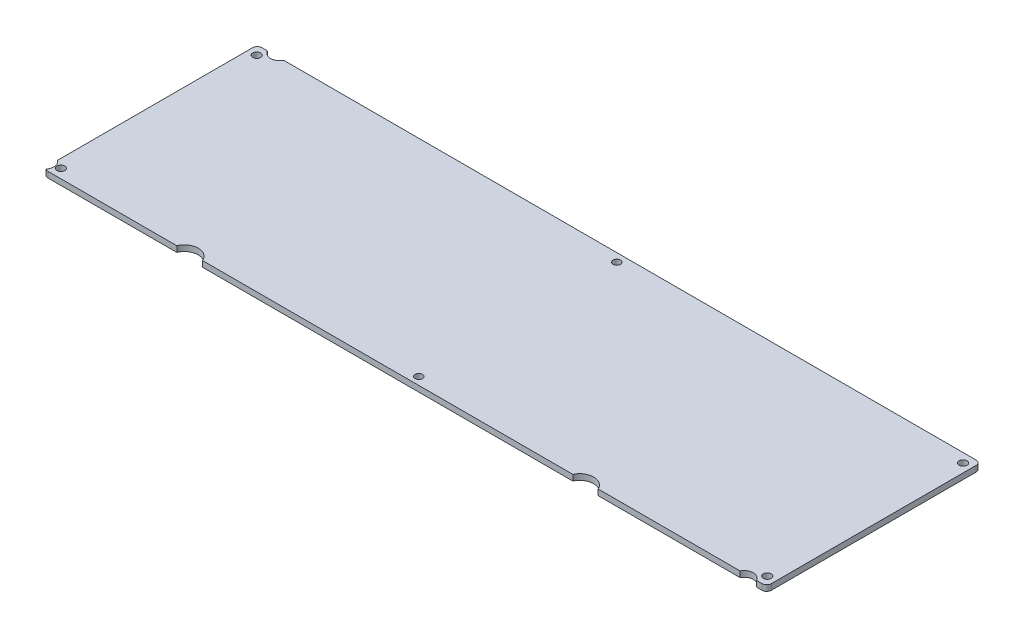
SolidWorks part; units mm, degrees
ref_plane "前视基准面" through (0, 0, 0) normal (0, 0, 1) x (1, 0, 0)
ref_plane "上视基准面" through (0, 0, 0) normal (0, 1, 0) x (1, 0, 0)
ref_plane "右视基准面" through (0, 0, 0) normal (1, 0, 0) x (0, 0, -1)
other "Configuration Table"
sketch "草图1" plane through (0, 0, 0) normal (0, 1, 0) x (1, 0, 0)
  line L0 (0, 46) -> (311, 46) construction
  line L1 (0, 92) -> (4.3709, 92)
  line L2 (0, 92) -> (0, 0)
  line L3 (0, 0) -> (299.5309, 0)
  line L4 (311, 92) -> (311, 0)
  line L5 (155.5, 92) -> (155.5, 0) construction
  line L6 (3.68, 88.095) -> (307.32, 88.095) construction
  line L7 (3.68, 3.905) -> (307.32, 3.905) construction
  line L8 (7.92, 93.845) -> (7.92, 87.3941) construction
  line L9 (11.4691, 92) -> (311, 92)
  line L10 (158.14, 88.415) -> (158.14, 3.315) construction
  line L11 (306.6291, 0) -> (311, 0)
  circle A0 centre (3.68, 88.095) radius 1.7
  circle A1 centre (307.32, 88.095) radius 1.7
  circle A2 centre (307.32, 3.905) radius 1.7
  circle A3 centre (3.68, 3.905) radius 1.7
  circle A4 centre (158.14, 88.415) radius 1.6
  circle A5 centre (158.14, 3.315) radius 1.6
  arc A6 (4.3709, 92) -> (11.4691, 92) centre (7.92, 93.845) ccw
  arc A8 (306.6291, 0) -> (299.5309, 0) centre (303.08, -1.845) ccw
  arc A10 (201.5, 197.1291) -> (201.5, 190.0309) centre (203.345, 193.58) ccw [skipped]
  arc A11 (109.5, -105.1291) -> (109.5, -98.0309) centre (107.655, -101.58) ccw [skipped]
  point P9 (3.68, 88.095)
  point P10 (307.32, 88.095)
  point P11 (3.68, 3.905)
  point P12 (307.32, 3.905)
  point P27 (155.5, 46)
  point P42 (155.5, 46)
  dimension "D5" = 3.4
  dimension "D7" = 3.2
  dimension "D9" = 3.2
  dimension "D12" = 8
  dimension "D15" = 4.24
  dimension "D1" = 311
  dimension "D2" = 92
  dimension "D3" = 303.64
  dimension "D4" = 84.19
  dimension "D6" = 0.32
  dimension "D8" = 0.59
  dimension "D10" = 4.24
  dimension "D11" = 5.75
  dimension "D13" = 2.64
  dimension "D14" = 4
extrude "凸台-拉伸1" add sketch "草图1" along normal blind 2.5
fillet "圆角1" radius 2 4 edges at (311, 1.25, -92) (0, 1.25, 0) (0, 1.25, -92) (311, 1.25, 0)
ref_plane "基准面1" through (155.5, 0, 0) normal (1, 0, 0) x (0, 0, -1)
ref_plane "基准面2" through (0, 0, -46) normal (0, 0, 1) x (1, 0, 0)
ref_axis "基准轴1" through (155.5, 2.625, -46) along (0, -1, 0)
sketch "草图2" plane through (0, 2.5, 0) normal (0, 1, 0) x (1, 0, 0)
  circle A0 centre (-2.32, 2.905) radius 4
  circle A1 centre (3.68, 3.905) radius 1.7 construction
  dimension "D1" = 8
  dimension "D2" = 6
  dimension "D3" = 1
extrude "切除-拉伸1" cut sketch "草图2" against normal through all
sketch "草图3" plane through (0, 2.5, 0) normal (0, 1, 0) x (1, 0, 0)
  circle A0 centre (233.1222, -2.5058) radius 6
  circle A1 centre (62.9423, -2.3087) radius 6
  ellipse E0 centre (233.1222, -2.5058) end of major axis (236.6222, -2.5098) minor radius 3.4915 (236.3316, -1.1129) -> (229.916, -1.1055) ccw construction
  ellipse E1 centre (62.9423, -2.3087) end of major axis (66.4423, -2.3127) minor radius 3.4915 (66.1518, -0.9158) -> (59.7362, -0.9084) ccw construction
  dimension "D1" = 12
  dimension "D2" = 12
extrude "切除-拉伸2" cut sketch "草图3" against normal through all
